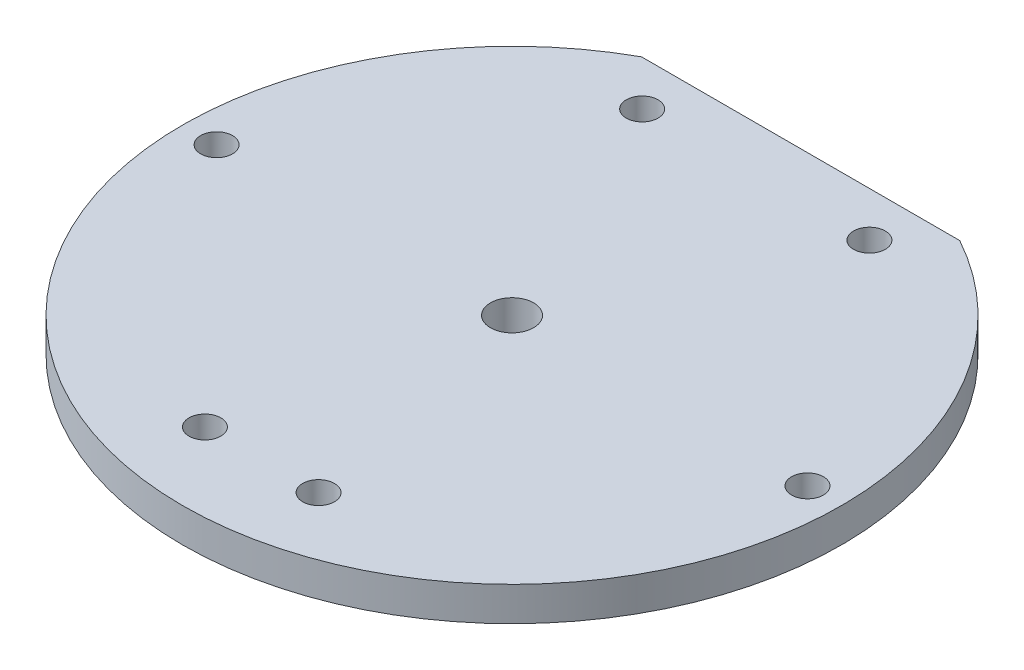
SolidWorks part; units mm, degrees
ref_plane "Front Plane" through (0, 0, 0) normal (0, 0, 1) x (1, 0, 0)
ref_plane "Top Plane" through (0, 0, 0) normal (0, 1, 0) x (1, 0, 0)
ref_plane "Right Plane" through (0, 0, 0) normal (1, 0, 0) x (0, 0, -1)
sketch "Sketch1" plane through (0, 0, 0) normal (0, 1, 0) x (1, 0, 0)
  circle A0 centre (0, 0) radius 29
extrude "Boss-Extrude1" add sketch "Sketch1" along normal blind 3
sketch "Sketch3" plane through (0, 0, 0) normal (0, -1, 0) x (1, 0, 0)
  circle A0 centre (0, 0) radius 4
extrude "Boss-Extrude2" add sketch "Sketch3" along normal blind 4
sketch "Sketch5" plane through (0, 3, 0) normal (0, 1, 0) x (1, 0, 0)
  line L0 (0, 0) -> (-15, 0)
  line L1 (0, 0) -> (15, 0)
  line L2 (-15, 0) -> (-15, 43.6226)
  line L3 (-15, 43.6226) -> (15, 43.6226)
  line L4 (15, 43.6226) -> (15, 0)
sketch "Sketch2" plane through (0, 3, 0) normal (0, 1, 0) x (1, 0, 0)
  circle A0 centre (0, 0) radius 1.9
extrude "Cut-Extrude1" cut sketch "Sketch2" against normal through all
sketch "Sketch4" plane through (0, 3, 0) normal (0, 1, 0) x (1, 0, 0)
  line L0 (0, 0) -> (0, -29) construction
  circle A5 centre (0, 0) radius 29 construction
  circle A8 centre (-5, -22.026) radius 1.4
  circle A9 centre (5, -22.026) radius 1.4
sketch "Sketch6" plane through (0, 3, 0) normal (0, 1, 0) x (1, 0, 0)
  line L0 (0, 0) -> (29, 0) construction
  circle A0 centre (0, 0) radius 29 construction
  circle A1 centre (26, 0) radius 1.4
  circle A2 centre (-26, 0) radius 1.4
  dimension "D1" = 26
extrude "Cut-Extrude3" cut sketch "Sketch6" against normal blind 10
sketch "Sketch7" plane through (0, 3, 0) normal (0, 1, 0) x (1, 0, 0)
  line L0 (0, 0) -> (0, 43.6226) construction
  line L1 (-15, 43.6226) -> (15, 43.6226) construction
  line L2 (0, 0) -> (0, 21.4517)
  line L3 (10, 21.4517) -> (-10, 21.4517)
  line L4 (0, 21.4517) -> (0, 25.3969)
  line L5 (-14, 25.3969) -> (14, 25.3969)
  circle A0 centre (-10, 21.4517) radius 1.4
  circle A1 centre (10, 21.4517) radius 1.4
  circle A2 centre (0, 0) radius 29 construction
  arc A3 (14, 25.3969) -> (-14, 25.3969) centre (0, 0) ccw
  circle M8 centre (0, 0) radius 29
  dimension "D1" = 20
  dimension "D2" = 28
extrude "Cut-Extrude4" cut sketch "Sketch7" against normal blind 10 contours A0 | A1 region at (-11.3604, 3, -21.4517) region at (10, 3, -22.8121)
extrude "Cut-Extrude5" cut sketch "Sketch7<3>" against normal blind 10 contours L5 L0 A3 | L0 L5 M8 region at (-5.2964, 3, -26.8461) region at (5.2964, 3, -26.8461)
sketch "Sketch7<3>" plane through (0, 3, 0) normal (0, 1, 0) x (1, 0, 0) same geometry as "Sketch7"
sketch "Sketch8" plane through (0, 3, 0) normal (0, 1, 0) x (1, 0, 0)
  line L0 (-14, 25.3969) -> (-14, 6.4277)
  line L1 (14, 25.3969) -> (14, 6.4277)
  line L2 (14, 6.4277) -> (28.2787, 6.4277)
  line L3 (-14, -6.5478) -> (-14, -25.3969)
  line L4 (-28.2511, -6.5478) -> (-14, -6.5478)
  line L5 (-28.2787, 6.4277) -> (-14, 6.4277)
  line L6 (14, -6.5478) -> (28.2511, -6.5478)
  line L7 (14, -6.5478) -> (14, -25.3969)
  arc A0 (-14, 25.3969) -> (14, 25.3969) centre (0, 0) ccw construction
  arc A1 (-14, 25.3969) -> (-28.2787, 6.4277) centre (0, 0) ccw
  arc A2 (14, -25.3969) -> (28.2511, -6.5478) centre (0, 0) ccw
  arc A3 (-28.2511, -6.5478) -> (-14, -25.3969) centre (0, 0) ccw
  arc A4 (28.2787, 6.4277) -> (14, 25.3969) centre (0, 0) ccw
extrude "Cut-Extrude6" [suppressed] cut sketch "Sketch8" against normal blind 10
extrude "Cut-Extrude7" cut sketch "Sketch4" against normal blind 10
